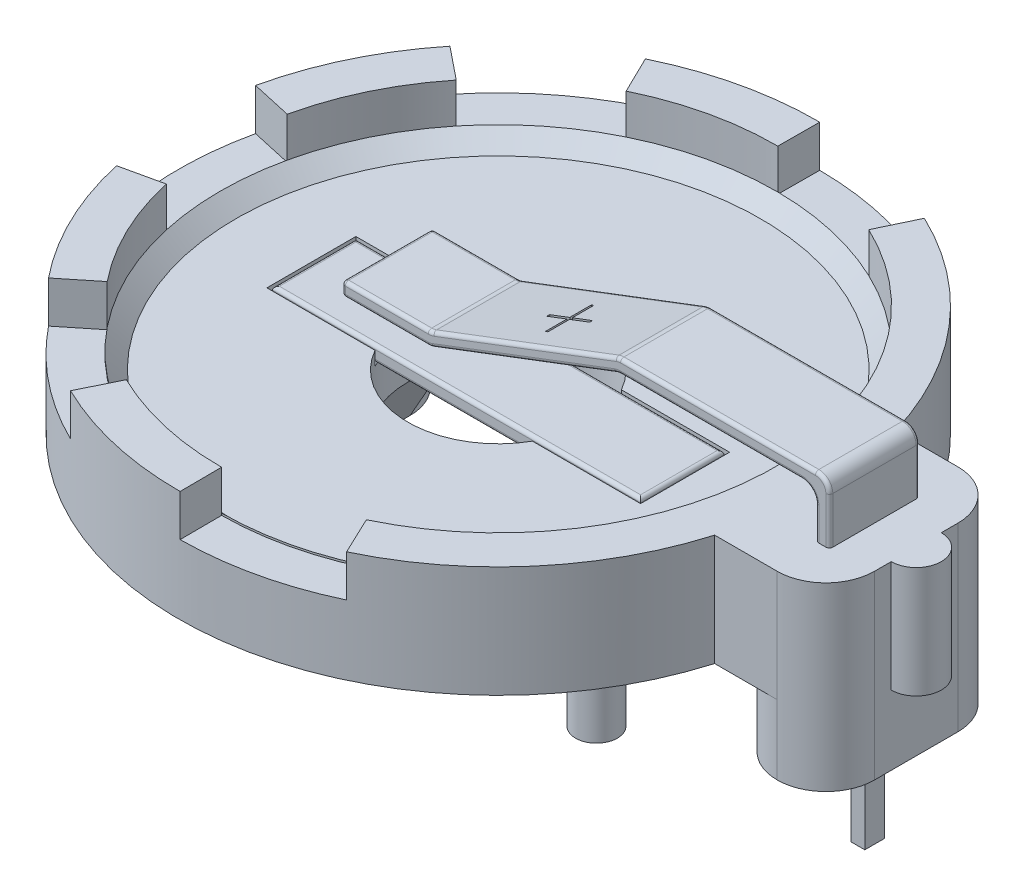
SolidWorks part; units mm, degrees
ref_plane "Front Plane" through (0, 0, 0) normal (0, 0, 1) x (1, 0, 0)
ref_plane "Top Plane" through (0, 0, 0) normal (0, 1, 0) x (1, 0, 0)
ref_plane "Right Plane" through (0, 0, 0) normal (1, 0, 0) x (0, 0, -1)
sketch "Sketch3" plane through (0, 0, 0) normal (0, 1, 0) x (1, 0, 0)
  line L0 (0, 0) -> (24.2923, 0) construction
  line L1 (11.0312, 3.25) -> (11.0312, -3.25) construction
  line L2 (15.0312, -3.25) -> (11.0312, -3.25)
  line L3 (15.0312, -3.25) -> (15.0312, 3.25)
  line L4 (15.0312, 3.25) -> (11.0312, 3.25)
  line L5 (0, -11.5) -> (0, 11.5) construction
  line L6 (15.0312, -3.25) -> (11.0312, 3.25) construction
  line L7 (15.0312, 3.25) -> (11.0312, -3.25) construction
  circle A0 centre (0, 0) radius 11.5 construction
  arc A1 (11.0312, 3.25) -> (11.0312, -3.25) centre (0, 0) ccw
  circle A2 centre (0, 0) radius 3.25
  point P3 (13.0312, 0)
  dimension "D1" = 23
  dimension "D4" = 6.5
  dimension "D2" = 4
  dimension "D3" = 6.5
extrude "Boss-Extrude2" add sketch "Sketch3" along normal blind 4
sketch "Sketch7" plane through (0, 4, 0) normal (0, 1, 0) x (1, 0, 0)
  circle A0 centre (0, 0) radius 10
  dimension "D1" = 20
extrude "Cut-Extrude1" cut sketch "Sketch7" against normal blind 2
chamfer "Chamfer3" distance 0.57 angle 45 1 edges at (0, 2, 10)
sketch "Sketch8" plane through (0, 4, 0) normal (0, 1, 0) x (1, 0, 0)
  line L0 (-11.5, 0) -> (-10, 0) construction
  line L1 (-9.7608, 2.1739) -> (-11.225, 2.5) construction
  line L2 (-9.7608, -2.1739) -> (-11.225, -2.5) construction
  line L3 (-11.225, 2.5) -> (-11.225, -2.5) construction
  line L4 (-11.225, 2.5) -> (-9.7608, 2.1739)
  line L5 (-11.225, -2.5) -> (-9.7608, -2.1739)
  line L6 (-5.0441, 10.3348) -> (-4.3862, 8.9867)
  line L7 (-8.9532, 7.2173) -> (-7.7854, 6.2759)
  line L8 (4.9351, 10.3872) -> (4.2914, 9.0324)
  line L9 (0.0605, 11.4998) -> (0.0526, 9.9999)
  line L10 (11.1981, 2.6179) -> (9.7374, 2.2764) [skipped]
  line L11 (9.0286, 7.1228) -> (7.851, 6.1937) [skipped]
  line L12 (9.0286, -7.1228) -> (7.851, -6.1937) [skipped]
  line L13 (11.1981, -2.6179) -> (9.7374, -2.2764) [skipped]
  line L14 (0.0605, -11.4998) -> (0.0526, -9.9999)
  line L15 (4.9351, -10.3872) -> (4.2914, -9.0324)
  line L16 (-8.9532, -7.2173) -> (-7.7854, -6.2759)
  line L17 (-5.0441, -10.3348) -> (-4.3862, -8.9867)
  arc A0 (11.0312, 3.25) -> (11.0312, -3.25) centre (0, 0) ccw construction
  circle A2 centre (0, 0) radius 10 construction
  arc A3 (-9.7608, 2.1739) -> (-9.7608, -2.1739) centre (0, 0) ccw
  arc A4 (-11.225, 2.5) -> (-11.225, -2.5) centre (0, 0) ccw
  arc A5 (-4.3862, 8.9867) -> (-7.7854, 6.2759) centre (0, 0) ccw
  arc A6 (-5.0441, 10.3348) -> (-8.9532, 7.2173) centre (0, 0) ccw
  arc A7 (4.2914, 9.0324) -> (0.0526, 9.9999) centre (0, 0) ccw
  arc A8 (4.9351, 10.3872) -> (0.0605, 11.4998) centre (0, 0) ccw
  arc A9 (9.7374, 2.2764) -> (7.851, 6.1937) centre (0, 0) ccw [skipped]
  arc A10 (11.1981, 2.6179) -> (9.0286, 7.1228) centre (0, 0) ccw [skipped]
  arc A11 (7.851, -6.1937) -> (9.7374, -2.2764) centre (0, 0) ccw [skipped]
  arc A12 (9.0286, -7.1228) -> (11.1981, -2.6179) centre (0, 0) ccw [skipped]
  arc A13 (0.0526, -9.9999) -> (4.2914, -9.0324) centre (0, 0) ccw
  arc A14 (0.0605, -11.4998) -> (4.9351, -10.3872) centre (0, 0) ccw
  arc A15 (-7.7854, -6.2759) -> (-4.3862, -8.9867) centre (0, 0) ccw
  arc A16 (-8.9532, -7.2173) -> (-5.0441, -10.3348) centre (0, 0) ccw
  dimension "D1" = 5
  dimension "D2" = 7
extrude "Cut-Extrude2" cut sketch "Sketch8" against normal blind 1.5
sketch "Sketch9" plane through (0, 0, 0) normal (0, -1, 0) x (1, 0, 0)
  line L1 (15.0312, -3.25) -> (11.0312, -3.25) construction
  line L2 (15.0312, 3.25) -> (11.5312, 3.25)
  line L3 (15.0312, 3.25) -> (15.0312, -3.25)
  line L4 (15.0312, -3.25) -> (11.5312, -3.25)
  line L6 (11.5312, 3.25) -> (11.5312, -3.25)
  line L7 (0, 0) -> (-7.9407, 0) construction
  line L8 (0, 11.5) -> (0, -11.5) construction
  line L9 (-8.1688, 3.25) -> (-4.6688, 3.25)
  line L10 (-8.1688, 3.25) -> (-8.1688, -3.25)
  line L11 (-8.1688, -3.25) -> (-4.6688, -3.25)
  line L12 (-4.6688, 3.25) -> (-4.6688, -3.25)
  line L13 (-8.1688, 3.25) -> (-4.6688, -3.25) construction
  line L14 (-8.1688, -3.25) -> (-4.6688, 3.25) construction
  arc A0 (11.0312, 3.25) -> (11.0312, -3.25) centre (0, 0) ccw construction
  circle A1 centre (0, -9.65) radius 0.75
  circle A2 centre (-8.3571, 4.825) radius 0.75
  circle A3 centre (8.3571, 4.825) radius 0.75
  point P9 (-6.4188, 0)
  dimension "D5" = 1.5
  dimension "D1" = 3.5
  dimension "D2" = 3.5
  dimension "D3" = 23.2
  dimension "D4" = 6.5
  dimension "D6" = 1.85
  dimension "D7" = 3
extrude "Boss-Extrude6" add sketch "Sketch9" along normal blind 2.5
fillet "Fillet1" radius 1.75 8 edges at (15.0312, 0.75, -3.25) (15.0312, 0.75, 3.25) (-4.6688, -1.25, -3.25) (-8.1688, -1.25, -3.25) (-4.6688, -1.25, 3.25) (-8.1688, -1.25, 3.25)
sketch "Sketch10" plane through (0, 0, 0) normal (0, 0, 1) x (1, 0, 0)
  line L1 (11.5312, -2.5) -> (13.2812, -2.5) construction
  line L3 (11.5312, 0) -> (10.2312, 0) construction
  line L4 (11.5312, 0) -> (11.5312, -2.5) construction
  line L5 (11.5312, -2.5) -> (10.2312, -2.5) construction
  line L6 (10.2312, 0) -> (10.2312, -2.5) construction
  line L7 (10.2312, 0) -> (11.5312, -2.5)
  dimension "D1" = 1.3
rib "Rib1" sketch "Sketch10" sketch "Sketch10" thickness 3 extrusion direction parallel to sketch draft on no parameters "D1"=3
sketch "Sketch12" plane through (0, 0, 0) normal (0, 0, 1) x (1, 0, 0)
  line L0 (-6.4188, -2.5) -> (-4.6688, -2.5) construction
  line L1 (-3.25, 0) -> (-4.6688, 0) construction
  line L2 (-3.25, 0) -> (-3.25, -2.5) construction
  line L3 (-3.25, -2.5) -> (-4.6688, -2.5) construction
  line L4 (-4.6688, 0) -> (-4.6688, -2.5) construction
  line L5 (-4.6688, 0) -> (-4.6688, -2.5) construction
  line L6 (-3.25, 0) -> (-4.6688, -2.5)
rib "Rib2" sketch "Sketch12" sketch "Sketch12" thickness 3 extrusion direction parallel to sketch draft on no parameters "D1"=3
sketch "Sketch13" plane through (0, -2.5, 0) normal (0, -1, 0) x (1, 0, 0)
  line L0 (13.2812, 3.25) -> (13.2812, -3.25) construction
  line L1 (15.0312, 0) -> (-8.1688, 0) construction
  line L2 (15.0312, -1.5) -> (15.0312, 1.5) construction
  line L3 (-8.1688, 1.5) -> (-8.1688, -1.5) construction
  line L4 (-6.9688, 0.35) -> (-6.4688, 0.35)
  line L5 (13.0312, 0.35) -> (13.5312, 0.35)
  line L6 (13.0312, 0.35) -> (13.0312, -0.35)
  line L7 (13.0312, -0.35) -> (13.5312, -0.35)
  line L8 (13.5312, 0.35) -> (13.5312, -0.35)
  line L9 (13.0312, 0.35) -> (13.5312, -0.35) construction
  line L10 (13.0312, -0.35) -> (13.5312, 0.35) construction
  line L11 (-6.9688, -0.35) -> (-6.4688, -0.35)
  line L12 (-6.4688, 0.35) -> (-6.4688, -0.35)
  line L13 (-6.9688, 0.35) -> (-6.9688, -0.35)
  line L14 (-6.9688, -0.35) -> (-6.4688, 0.35) construction
  line L15 (-6.9688, 0.35) -> (-6.4688, -0.35) construction
  point P10 (13.2812, 0)
  point P15 (-6.7188, 0)
  dimension "D1" = 0.7
  dimension "D2" = 0.5
  dimension "D3" = 2
extrude "Boss-Extrude7" add sketch "Sketch13" along normal blind 3.5 separate body
sketch "Sketch14" plane through (0, 2, 0) normal (0, 1, 0) x (1, 0, 0)
  line L0 (-6.9688, 0.35) -> (-6.4688, 0.35) construction
  line L1 (-6.9688, -0.35) -> (-6.9688, 0.35) construction
  line L2 (-6.4688, -0.35) -> (-6.9688, -0.35) construction
  line L3 (-6.4688, 0.35) -> (-6.4688, -0.35) construction
  line L8 (-6.9688, 0.35) -> (-6.4688, 0.35) construction
  line L9 (-6.9688, -0.35) -> (-6.9688, 0.35) construction
  line L10 (-6.4688, -0.35) -> (-6.9688, -0.35) construction
  line L11 (-6.4688, 0.35) -> (-6.4688, -0.35) construction
  line L12 (-6.9688, 0.35) -> (-6.4688, -0.35) construction
  line L13 (2.8289, 1.6) -> (6.7189, 1.6)
  line L14 (2.8289, 1.6) -> (2.8289, -1.6) construction
  line L15 (2.8289, -1.6) -> (6.7189, -1.6)
  line L16 (-11.5, 0) -> (15.0312, 0) construction
  line L17 (15.0312, -1.5) -> (15.0312, 1.5) construction
  line L18 (6.7189, 1.6) -> (6.7189, -1.6)
  line L19 (2.8289, 1.6) -> (6.7189, -1.6) construction
  line L20 (2.8289, -1.6) -> (6.7189, 1.6) construction
  line L21 (-6.7188, 1.6) -> (-2.8289, 1.6)
  line L22 (-6.7188, 1.6) -> (-6.7188, -1.6)
  line L23 (-6.7188, -1.6) -> (-2.8289, -1.6)
  line L24 (-2.8289, 1.6) -> (-2.8289, -1.6) construction
  line L25 (-6.7188, 1.6) -> (-2.8289, -1.6) construction
  line L26 (-6.7188, -1.6) -> (-2.8289, 1.6) construction
  line L27 (-6.9688, -0.35) -> (-6.4688, 0.35) construction
  arc A0 (-11.225, 2.5) -> (-11.225, -2.5) centre (0, 0) ccw construction
  circle A1 centre (0, 0) radius 3.25 construction
  arc A2 (-2.8289, 1.6) -> (-2.8289, -1.6) centre (0, 0) ccw
  arc A3 (2.8289, -1.6) -> (2.8289, 1.6) centre (0, 0) ccw
  point P4 (4.7739, 0)
  point P18 (-4.7738, 0)
  point P23 (-6.7188, 0)
  dimension "D1" = 3.2
  dimension "D2" = 3.89
  dimension "D3" = 3.2
extrude "Cut-Extrude3" cut sketch "Sketch14" against normal blind 0.5
sketch "Sketch15" plane through (0, 1.5, 0) normal (0, 1, 0) x (1, 0, 0)
  line L0 (-2.8289, 1.6) -> (-6.7188, 1.6) construction
  line L1 (-6.6188, 1.5) -> (6.6189, 1.5)
  line L2 (-6.6188, 1.5) -> (-6.6188, -1.5)
  line L3 (-6.6188, -1.5) -> (6.6189, -1.5)
  line L4 (6.6189, 1.5) -> (6.6189, -1.5)
  line L5 (-6.7188, 1.6) -> (-6.7188, -1.6) construction
  line L6 (-6.7188, -1.6) -> (-2.8289, -1.6) construction
  line L7 (6.7189, -1.6) -> (6.7189, 1.6) construction
  dimension "D1" = 0.1
  dimension "D2" = 0.1
  dimension "D3" = 0.1
  dimension "D4" = 0.1
extrude "Boss-Extrude8" add sketch "Sketch15" along normal blind 0.55 separate body
sketch "Sketch16" plane through (0, 0, 0) normal (0, 0, 1) x (1, 0, 0)
  line L0 (13.5312, -6) -> (13.0312, -6) construction
  line L1 (13.5312, -6) -> (13.0312, -6) construction
  line L2 (13.2812, -6) -> (13.2812, 9.6729) construction
  line L3 (13.2812, 5.67) -> (5.9312, 5.67) construction
  line L4 (13.2812, 6.17) -> (5.9312, 6.17)
  line L5 (11.0312, 4) -> (13.2812, 4) construction
  line L6 (5.9312, 6.17) -> (-0.799, 3.6118)
  line L7 (13.5312, 4) -> (13.0312, 4)
  line L8 (13.5312, 4) -> (13.5312, 6.17)
  line L9 (13.5312, 6.17) -> (13.0312, 6.17) construction
  line L10 (13.0312, 4) -> (13.0312, 6.17) construction
  line L11 (13.5312, 4) -> (13.0312, 6.17) construction
  line L12 (13.5312, 6.17) -> (13.0312, 4) construction
  line L13 (5.9312, 5.67) -> (-0.799, 3.1118)
  line L14 (-0.799, 3.6118) -> (-3.999, 3.6118)
  line L15 (-3.999, 3.6118) -> (-3.999, 3.1118)
  line L16 (-3.999, 3.1118) -> (-0.799, 3.1118)
  line L17 (5.9312, 5.67) -> (13.0312, 5.67)
  line L18 (13.0312, 5.67) -> (13.0312, 4)
  line L20 (13.2812, 6.17) -> (13.5312, 6.17)
  point P11 (13.2812, 5.085)
  dimension "D1" = 1.67
  dimension "D2" = 0.5
  dimension "D3" = 0.5
  dimension "D4" = 7.6
  dimension "D5" = 0.5
  dimension "D6" = 7.2
  dimension "D7" = 0.5
  dimension "D8" = 3.2
  dimension "D9" = 20.812
  dimension "D10" = 20.812
extrude "Boss-Extrude9" add sketch "Sketch16" along normal mid plane 3.25 separate body
fillet "Fillet2" radius 0.5 6 edges at (-0.799, 3.1118, 0) (-0.799, 3.6118, 0) (5.9312, 5.67, 0) (5.9312, 6.17, 0) (13.0312, 5.67, 0) (13.5312, 6.17, 0)
fillet "Fillet3" radius 0.125 32 edges at (13.0312, 4.585, 1.625) (12.8848, 5.5236, 1.625) (9.2771, 5.67, 1.625) (5.9327, 5.6618, 1.625) (2.5661, 4.3909, 1.625) (-0.8005, 3.1201, 1.625) (13.0312, 4.585, -1.625) (12.8848, 5.5236, -1.625) (9.2771, 5.67, -1.625) (5.9327, 5.6618, -1.625) (2.5661, 4.3909, -1.625) (-0.8005, 3.1201, -1.625) (13.5312, 4.835, -1.625) (13.3848, 6.0236, -1.625) (9.5271, 6.17, -1.625) (5.9327, 6.1618, -1.625) (2.5661, 4.8909, -1.625) (-0.8005, 3.6201, -1.625) (13.5312, 4.835, 1.625) (13.3848, 6.0236, 1.625) (9.5271, 6.17, 1.625) (5.9327, 6.1618, 1.625) (2.5661, 4.8909, 1.625) (-0.8005, 3.6201, 1.625) (-3.999, 3.1118, 0) (-2.4449, 3.1118, 1.625) (-2.4449, 3.1118, -1.625) (-3.999, 3.6118, 0) (-2.4449, 3.6118, -1.625) (-2.4449, 3.6118, 1.625) (-3.999, 3.3618, -1.625) (-3.999, 3.3618, 1.625)
fillet "Fillet4" radius 0.125 8 edges at (0, 1.5, 1.5) (6.6189, 1.5, 0) (0, 1.5, -1.5) (-6.6188, 1.5, 0) (0, 2.05, -1.5) (6.6189, 2.05, 0) (0, 2.05, 1.5) (-6.6188, 2.05, 0)
sketch "Sketch18" plane through (-1.3004, 3.4213, 0) normal (-0.3553, 0.9348, 0) x (0.9348, 0.3553, 0)
  line L0 (-999.3718, 0) -> (49000.6282, 0) construction
  line L1 (0.6282, 1.5) -> (0.6282, -1.5) construction
  line L2 (4.1364, -998.5) -> (4.1364, 49001.5) construction
  line L3 (7.6446, 1.5) -> (0.6282, 1.5) construction
  line L4 (4.0864, 0.05) -> (3.3114, 0.05)
  line L5 (4.0864, 0.825) -> (4.1864, 0.825) construction
  line L6 (4.0864, 0.825) -> (4.0864, -0.825) construction
  line L7 (4.0864, -0.825) -> (4.1864, -0.825) construction
  line L8 (4.1864, 0.825) -> (4.1864, -0.825) construction
  line L9 (4.0864, 0.825) -> (4.1864, -0.825) construction
  line L10 (4.0864, -0.825) -> (4.1864, 0.825) construction
  line L11 (3.3114, 0.05) -> (4.9614, 0.05) construction
  line L12 (3.3114, 0.05) -> (3.3114, -0.05) construction
  line L13 (3.3114, -0.05) -> (4.9614, -0.05) construction
  line L14 (4.9614, 0.05) -> (4.9614, -0.05) construction
  line L15 (3.3114, 0.05) -> (4.9614, -0.05) construction
  line L16 (3.3114, -0.05) -> (4.9614, 0.05) construction
  line L17 (3.3114, 0.05) -> (3.3114, -0.05)
  line L18 (3.3114, -0.05) -> (4.0864, -0.05)
  line L19 (4.0864, -0.05) -> (4.0864, -0.825)
  line L20 (4.0864, -0.825) -> (4.1864, -0.825)
  line L21 (4.1864, -0.825) -> (4.1864, -0.05)
  line L22 (4.9614, 0.05) -> (4.1864, 0.05)
  line L23 (4.1864, 0.05) -> (4.1864, 0.825)
  line L24 (4.1864, 0.825) -> (4.0864, 0.825)
  line L25 (4.0864, 0.825) -> (4.0864, 0.05)
  line L26 (4.9614, 0.05) -> (4.9614, -0.05)
  line L27 (4.9614, -0.05) -> (4.1864, -0.05)
  point P5 (0.6282, 0)
  point P6 (4.1364, 0)
  point P10 (4.1364, 1.5)
  point P15 (4.1364, 0)
  dimension "D1" = 1.65
  dimension "D2" = 1.65
  dimension "D3" = 0.1
  dimension "D4" = 0.1
extrude "Cut-Extrude4" cut sketch "Sketch18" against normal blind 0.125
sketch "Sketch20" plane through (0, 4, 0) normal (0, 1, 0) x (1, 0, 0)
  line L0 (15.0312, -1.5) -> (15.0312, 1.5) construction
  line L1 (15.0312, -1.5) -> (15.0312, 1.5) construction
  line L2 (15.0312, 0.9) -> (15.0312, -0.9)
  arc A0 (15.0312, 0.9) -> (15.0312, -0.9) centre (15.0312, 0) cw
  dimension "D1" = 0.9
extrude "Boss-Extrude10" add sketch "Sketch20" against normal blind 4
